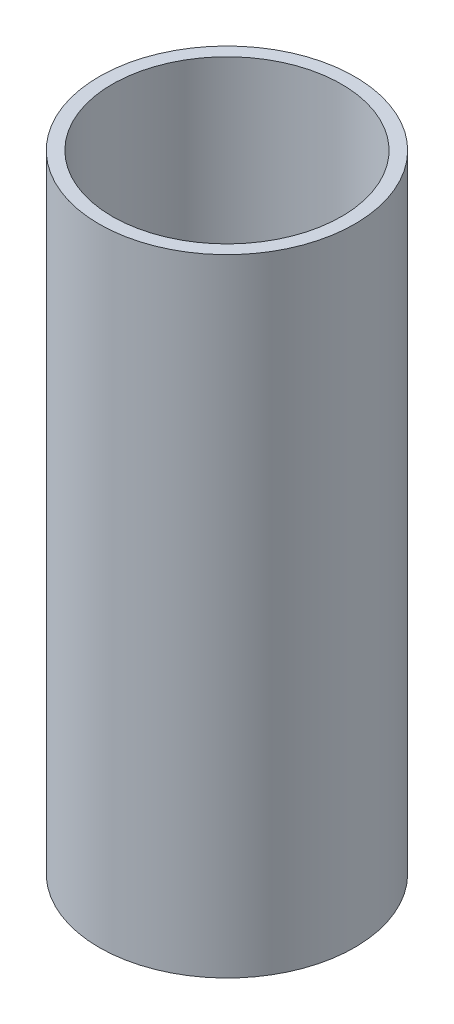
SolidWorks part; units mm, degrees
ref_plane "Front Plane" through (0, 0, 0) normal (0, 0, 1) x (1, 0, 0)
ref_plane "Top Plane" through (0, 0, 0) normal (0, 1, 0) x (1, 0, 0)
ref_plane "Right Plane" through (0, 0, 0) normal (1, 0, 0) x (0, 0, -1)
sketch "Sketch1" plane through (0, 0, 0) normal (0, 1, 0) x (1, 0, 0)
  circle A0 centre (0, 0) radius 40
  dimension "SLEEVE_OD" = 80
extrude "Boss-Extrude1" add sketch "Sketch1" along normal blind 196.0988
sketch "Sketch2" plane through (0, 0, 0) normal (0, 1, 0) x (1, 0, 0)
  circle A0 centre (0, 0) radius 35.885
  dimension "BORE_D" = 71.77
extrude "Cut-Extrude1" cut sketch "Sketch2" along normal through all
chamfer "Chamfer1" distance 3.8967 angle 30 rebuild error yes
